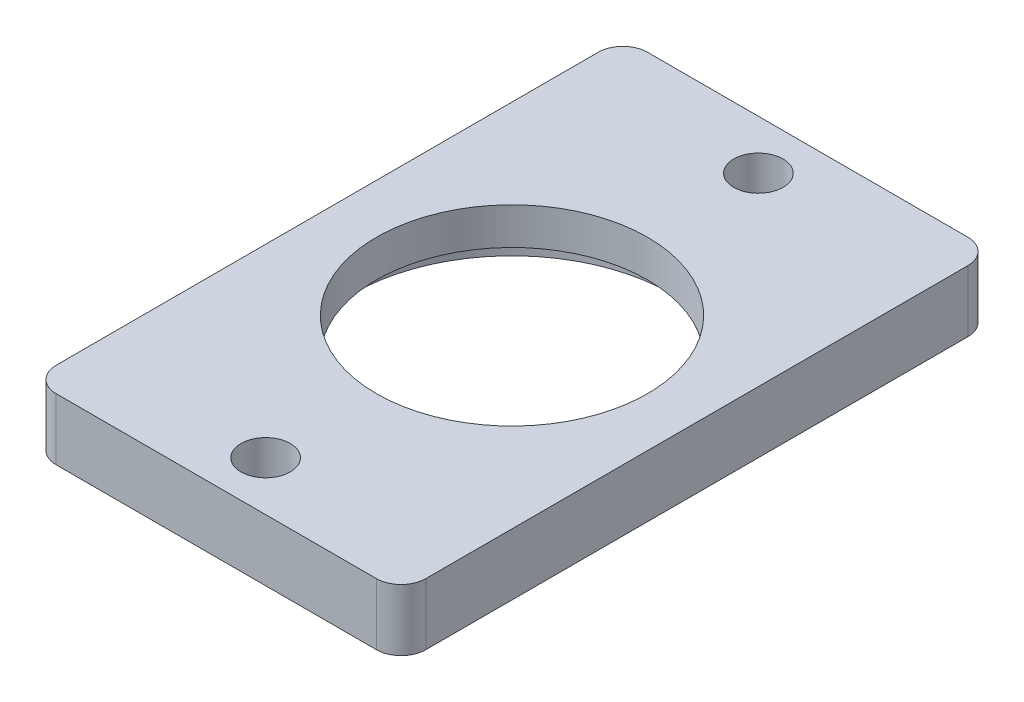
SolidWorks part; units mm, degrees
ref_plane "前视基准面" through (0, 0, 0) normal (0, 0, 1) x (1, 0, 0)
ref_plane "上视基准面" through (0, 0, 0) normal (0, 1, 0) x (1, 0, 0)
ref_plane "右视基准面" through (0, 0, 0) normal (1, 0, 0) x (0, 0, -1)
sketch "草图1" plane through (0, 0, 0) normal (0, 1, 0) x (1, 0, 0)
  line L0 (-15, 0) -> (-15, 22)
  line L1 (-13, 24) -> (13, 24)
  line L2 (-15, 0) -> (-15, -22)
  line L4 (15, -22) -> (15, 22)
  line L6 (-15, 22) -> (-15, -22)
  line L8 (-13, -24) -> (13, -24)
  circle A0 centre (0, 0) radius 11
  circle A1 centre (0, 20) radius 2
  circle A2 centre (0, -20) radius 2
  arc A3 (-13, -24) -> (-15, -22) centre (-13, -22) cw
  arc A4 (13, -24) -> (15, -22) centre (13, -22) ccw
  arc A5 (15, 22) -> (13, 24) centre (13, 22) ccw
  arc A6 (-15, 22) -> (-13, 24) centre (-13, 22) cw
  circle A7 centre (0, 0) radius 13
  dimension "D1" = 2
extrude "凸台-拉伸1" add sketch "草图1" along normal blind 5 contours A6 L0 L2 A3 L8 A4 L4 A5 L1 A2 A1 A0 | A7 A0 region at (-14.434, 0, -11) region at (-12.6323, 0, 0)
extrude "切除-拉伸1" cut sketch "草图1<4>" along normal blind 2 contours A7 A0 region at (-12.6323, 0, 0)
sketch "草图1<4>" plane through (0, 0, 0) normal (0, 1, 0) x (1, 0, 0) same geometry as "草图1"
